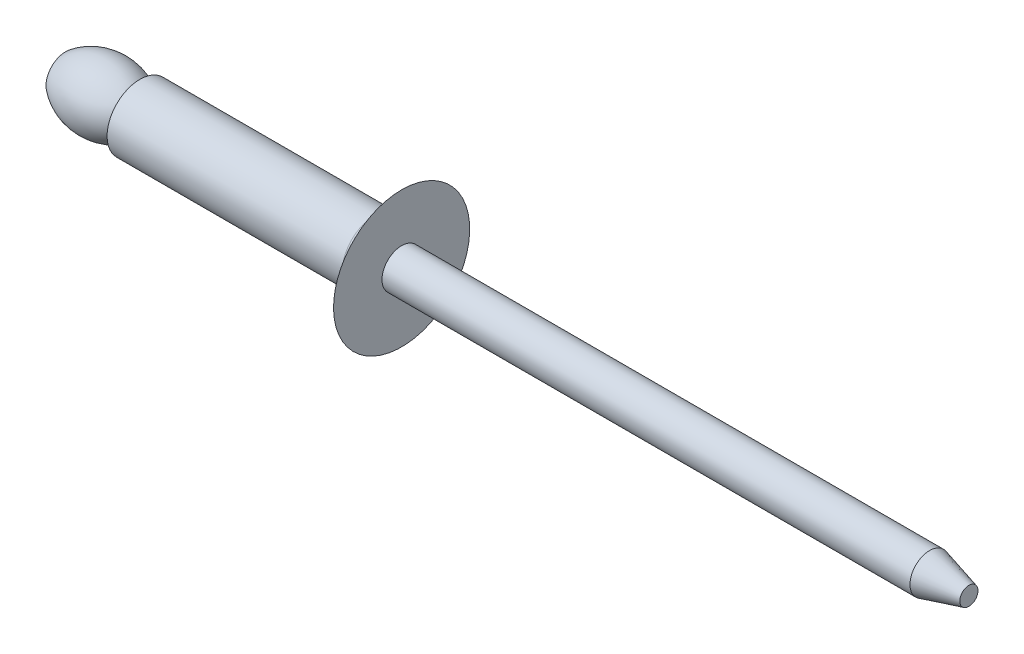
SolidWorks part; units mm, degrees
ref_plane "Front" through (0, 0, 0) normal (0, 0, 1) x (1, 0, 0)
ref_plane "Top" through (0, 0, 0) normal (0, 1, 0) x (1, 0, 0)
ref_plane "Right" through (0, 0, 0) normal (1, 0, 0) x (0, 0, -1)
sketch "Sketch1" plane through (-30.2384, 33.3584, 0) normal (0, 0, 1) x (0, -1, 0)
  line L0 (34.2584, 33.6384) -> (34.8584, 33.6384)
  line L1 (34.8584, 33.6384) -> (34.8584, 44.7031)
  line L2 (34.8584, 44.7031) -> (36.4784, 45.6384)
  line L3 (36.4784, 45.6384) -> (34.2584, 45.6384)
  line L4 (34.2584, 45.6384) -> (34.2584, 71.6384)
  line L5 (33.3584, 73.8835) -> (33.3584, -10.2868) construction
  line L6 (34.2584, 71.6384) -> (33.3584, 71.6384)
  line L7 (33.3584, 71.6384) -> (33.3584, 30.2384)
  line L8 (34.2584, 30.2384) -> (33.3584, 30.2384)
  arc A0 (34.2584, 33.6384) -> (34.2584, 30.2384) centre (32.15, 31.9384) cw
  dimension "D3" = 60
  dimension "l2" = 3.4
revolve "Base-Revolve" add sketch "Sketch1" angle 360 about L5
fillet "Fillet1" radius 0.5 1 edges at (14.4647, 1.5, 0)
chamfer "Chamfer1" distance 1.8 angle 15 1 edges at (41.4, 0.9, 0) first distance on face at (41.4, 0.9, 0)
equation "\"D1@Chamfer1\" = \"d1@Sketch1\""
